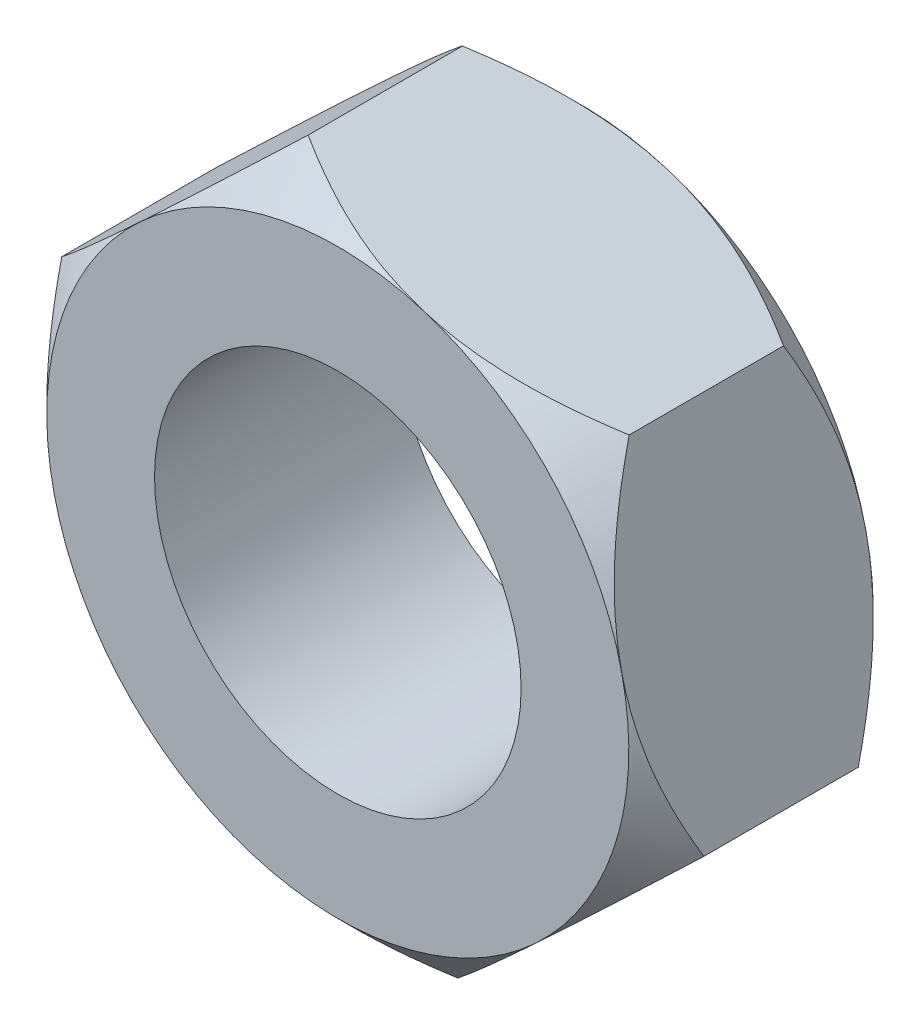
SolidWorks part; units mm, degrees
material "Alloy Steel"
ref_plane "Front Plane" through (0, 0, 0) normal (0, 0, 1) x (1, 0, 0)
ref_plane "Top Plane" through (0, 0, 0) normal (0, 1, 0) x (1, 0, 0)
ref_plane "Right Plane" through (0, 0, 0) normal (1, 0, 0) x (0, 0, -1)
sketch "Sketch1" plane through (0, 0, 0) normal (0, 0, 1) x (1, 0, 0)
  line L1 (2.6277, -0.8111) -> (2.0162, 1.8701)
  line L2 (2.0162, 1.8701) -> (-0.6114, 2.6812)
  line L3 (-0.6114, 2.6812) -> (-2.6277, 0.8111)
  line L4 (-2.6277, 0.8111) -> (-2.0162, -1.8701)
  line L5 (-2.0162, -1.8701) -> (0.6114, -2.6812)
  line L6 (0.6114, -2.6812) -> (2.6277, -0.8111)
  circle A0 centre (0, 0) radius 2.3816 construction
  dimension "D1" = 5.5
extrude "Boss-Extrude1" add sketch "Sketch1" against normal blind 1 and the other way blind 1
sketch "Sketch2" plane through (0, 0, 1) normal (0, 0, 1) x (1, 0, 0)
  circle A0 centre (0, 0) radius 1.5
  dimension "D1" = 3
extrude "Cut-Extrude1" cut sketch "Sketch2" against normal up to next
sketch "Sketch19" plane through (0, 0, 1) normal (0, 0, 1) x (1, 0, 0)
  line L0 (-2.0162, -1.8701) -> (0.6114, -2.6812) construction
  circle A0 centre (0, 0) radius 2.3816
extrude "Cut-Extrude7" cut sketch "Sketch19" against normal blind 0.75 draft 45 flip side to cut contours A0
mirror "Mirror1" about plane through (0, 0, 0) normal (0, 0, 1) of "Cut-Extrude7"
